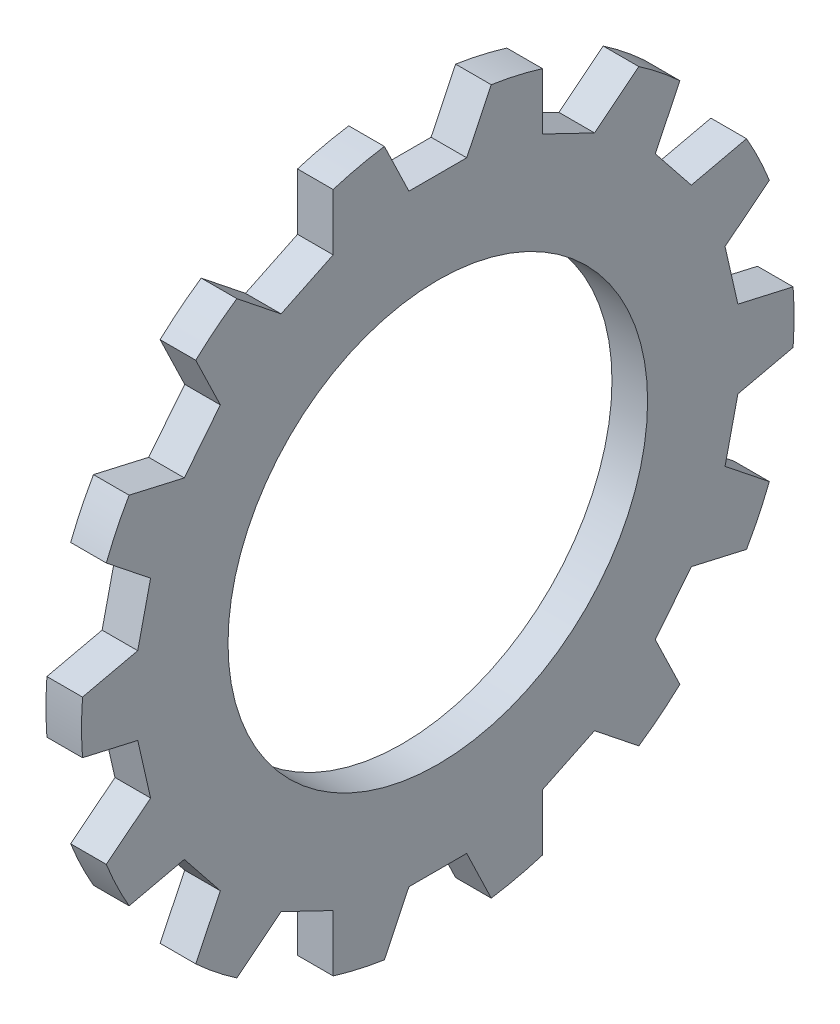
SolidWorks part; units mm, degrees
extrude "Base-Extrude" add sketch "Sketch1" against normal blind 1.143
sketch "Sketch1" plane through (0, 0, 0) normal (1, 0, 0) x (0, 0, -1)
  circle A0 centre (0, 0) radius 6.731
  circle A1 centre (0, 0) radius 11.43
  dimension "InsideDia" = 13.462
  dimension "OutsideDia" = 22.86
ref_plane "Plane1" through (0, 0, 0) normal (0, 0, 1) x (1, 0, 0)
ref_plane "Plane2" through (0, 0, 0) normal (0, 1, 0) x (1, 0, 0)
ref_plane "Plane3" through (0, 0, 0) normal (1, 0, 0) x (0, 0, -1)
sketch "Sketch3" plane through (0, 0, 0) normal (1, 0, 0) x (0, 0, -1)
  line L0 (0.9271, 9.6633) -> (1.7145, 11.3007)
  line L1 (-0.9271, 9.6633) -> (-1.7145, 11.3007)
  line L2 (-1.7145, 11.3007) -> (-1.7145, 12.3294)
  line L3 (-1.7145, 12.3294) -> (1.7145, 12.3294)
  line L4 (1.7145, 12.3294) -> (1.7145, 11.3007)
  line L5 (-0.9271, 9.6633) -> (0.9271, 9.6633)
  arc A0 (-0.9271, 9.6633) -> (0.9271, 9.6633) centre (0, 10.1092) ccw construction
  circle A1 centre (0, 0) radius 11.43 construction
  circle A2 centre (0, 0) radius 9.0805 construction
  dimension "D1" = 2.0574
  dimension "D4" = 18.161
  dimension "D2" = 3.429
  dimension "D3" = 1.0287
  dimension "D5" = 1.7145
extrude "TypeASlot" cut sketch "Sketch3" against normal through all
pattern_circular "TypeAPattern" count 14 over 360 about axis through (-1.143, 0, 0) along (1, 0, 0) of "TypeASlot"
equation "\"D1@Sketch3\" = \"OutsideDia@Sketch1\" * .09"
equation "\"D2@Sketch3\" = \"OutsideDia@Sketch1\" * .15"
equation "\"D3@Sketch3\" = \"D1@Sketch3\" / 2"
equation "\"D4@Sketch3\" = \"InsideDia@Sketch1\" +  ( \"OutsideDia@Sketch1\" - \"InsideDia@Sketch1\" )  / 2"
equation "\"D5@Sketch3\" = \"D2@Sketch3\" / 2"
